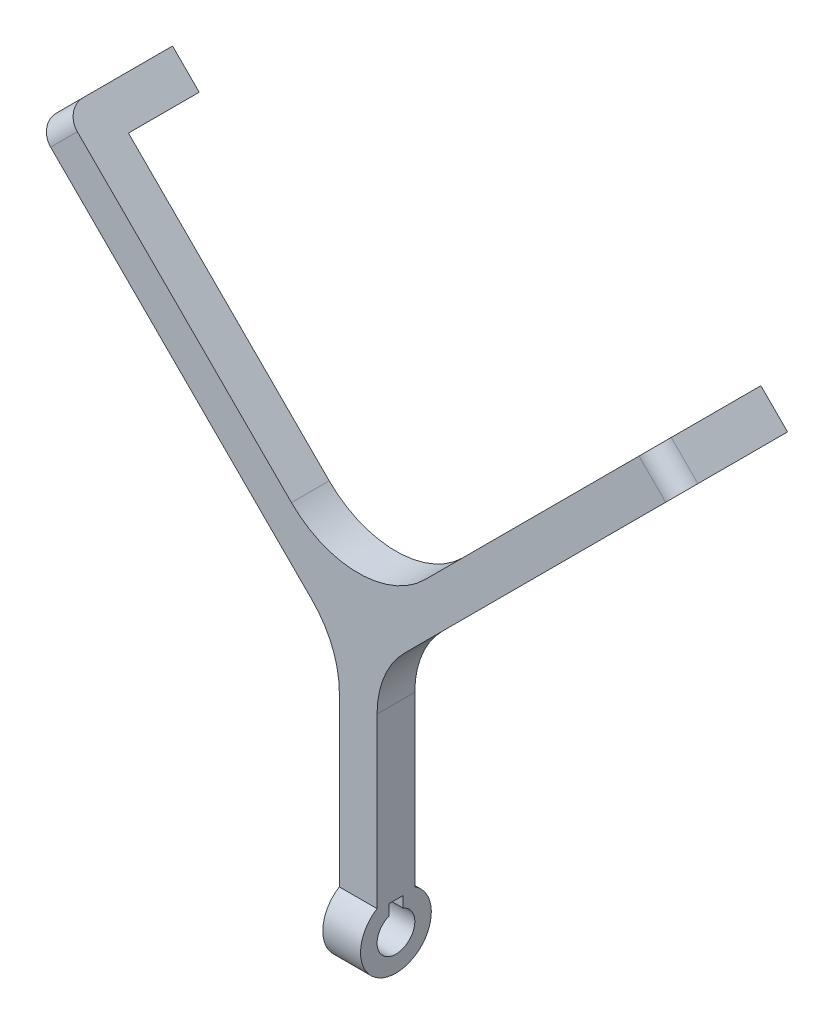
SolidWorks part; units mm, degrees
material "PLA"
ref_plane "Plan de face" through (0, 0, 0) normal (0, 0, 1) x (1, 0, 0)
ref_plane "Plan de dessus" through (0, 0, 0) normal (0, 1, 0) x (1, 0, 0)
ref_plane "Plan de droite" through (0, 0, 0) normal (1, 0, 0) x (0, 0, -1)
sketch "Esquisse1" plane through (0, 0, 0) normal (0, 0, 1) x (1, 0, 0)
  line L1 (0, 0) -> (136, 0) construction
  line L2 (0, 0) -> (0, 120) construction
  line L3 (0, 120) -> (136, 120) construction
  line L4 (136, 0) -> (136, 120) construction
  line L16 (64, 0) -> (64, 50.3431)
  line L17 (64, 50.3431) -> (0, 114.3431)
  line L18 (0, 114.3431) -> (5.6569, 120)
  line L19 (5.6569, 120) -> (68, 57.6569)
  line L20 (68, 57.6569) -> (130.3431, 120)
  line L21 (130.3431, 120) -> (136, 114.3431)
  line L22 (136, 114.3431) -> (72, 50.3431)
  line L23 (72, 50.3431) -> (72, 0)
  line L24 (72, 0) -> (64, 0)
  point P19 (68, 0)
  dimension "D1" = 136
  dimension "D2" = 120
  dimension "D3" = 8
  dimension "D4" = 68
  dimension "D5" = 135
  dimension "D6" = 135
  dimension "D7" = 90
  dimension "D8" = 8
  dimension "D9" = 8
  dimension "D10" = 68
extrude "Boss.-Extru.1" add sketch "Esquisse1" along normal blind 8
sketch "Esquisse2" plane through (0, 0, 0) normal (0, 0, -1) x (-1, 0, 0)
  line L0 (-72, 50.3431) -> (-136, 114.3431) construction
  line L1 (-136, 114.3431) -> (-130.3431, 120) construction
  line L2 (-130.3431, 120) -> (-68, 57.6569) construction
  line L3 (-130.3431, 108.6863) -> (-136, 114.3431)
  line L4 (-136, 114.3431) -> (-130.3431, 120)
  line L5 (-130.3431, 120) -> (-124.6863, 114.3431)
  line L6 (-130.3431, 108.6863) -> (-124.6863, 114.3431)
  line L7 (0, 114.3431) -> (-64, 50.3431) construction
  line L8 (-68, 57.6569) -> (-5.6569, 120) construction
  line L9 (-5.6569, 120) -> (0, 114.3431) construction
  line L10 (0, 114.3431) -> (-5.6569, 108.6863)
  line L11 (-11.3137, 114.3431) -> (-5.6569, 120)
  line L12 (-5.6569, 120) -> (0, 114.3431)
  line L13 (-11.3137, 114.3431) -> (-5.6569, 108.6863)
  dimension "D1" = 8
  dimension "D2" = 8
extrude "Boss.-Extru.2" add sketch "Esquisse2" along normal blind 15
fillet "Congé1" radius 20 3 edges at (72, 50.3431, 4) (64, 50.3431, 4) (68, 57.6569, 4)
fillet "Congé2" radius 4 2 edges at (133.1716, 117.1716, 8) (2.8284, 117.1716, 8)
sketch "Esquisse3" plane through (64, 0, 0) normal (-1, 0, 0) x (0, 0, 1)
  line L0 (4, 0) -> (4, 33.6289) construction
  line L1 (8, 0) -> (0, 0) construction
  circle A0 centre (4, 0) radius 7.5
  dimension "D1" = 15
extrude "Boss.-Extru.3" add sketch "Esquisse3" against normal up to surface (8 mm away) up to face at (72, 21.0294, 4)
sketch "Esquisse4" plane through (64, 0, 0) normal (-1, 0, 0) x (0, 0, 1)
  line L5 (2.5, 3.7081) -> (2.5, 6)
  line L7 (4, 0) -> (4, 7.4852) construction
  line L9 (2.5, 6) -> (5.5, 6)
  line L10 (5.5, 3.7081) -> (5.5, 6)
  arc A0 (2.5, 3.7081) -> (5.5, 3.7081) centre (4, 0) ccw
  point P10 (4, 6)
  point P11 (4, 6)
  dimension "D1" = 8
  dimension "D2" = 3
  dimension "D3" = 6
extrude "Enlèv. mat.-Extru.1" cut sketch "Esquisse4" against normal through all
equation "\"long_tot\"= 120"
equation "\"espac_sub_arms\"= 120"
equation "\"épaiss_cadre\"= 8"
equation "\"long_protub\"= 15"
equation "\"rayon_conge\"= 3"
equation "\"diam_axe\"= 5"
equation "\"D1@Esquisse1\"=\"espac_sub_arms\"+\"épaiss_cadre\"*2"
equation "\"D2@Esquisse1\"=\"long_tot\""
equation "\"D3@Esquisse1\"=\"épaiss_cadre\""
equation "\"D4@Esquisse1\"=\"D1@Esquisse1\"/2"
equation "\"D6@Esquisse1\"=\"D5@Esquisse1\""
equation "\"D8@Esquisse1\"=\"épaiss_cadre\""
equation "\"D9@Esquisse1\"=\"épaiss_cadre\""
equation "\"D10@Esquisse1\"=\"D4@Esquisse1\""
equation "\"D1@Boss.-Extru.1\"=\"épaiss_cadre\""
equation "\"D1@Esquisse2\"=\"épaiss_cadre\""
equation "\"D2@Esquisse2\"=\"épaiss_cadre\""
equation "\"D1@Boss.-Extru.2\"=\"long_protub\""
